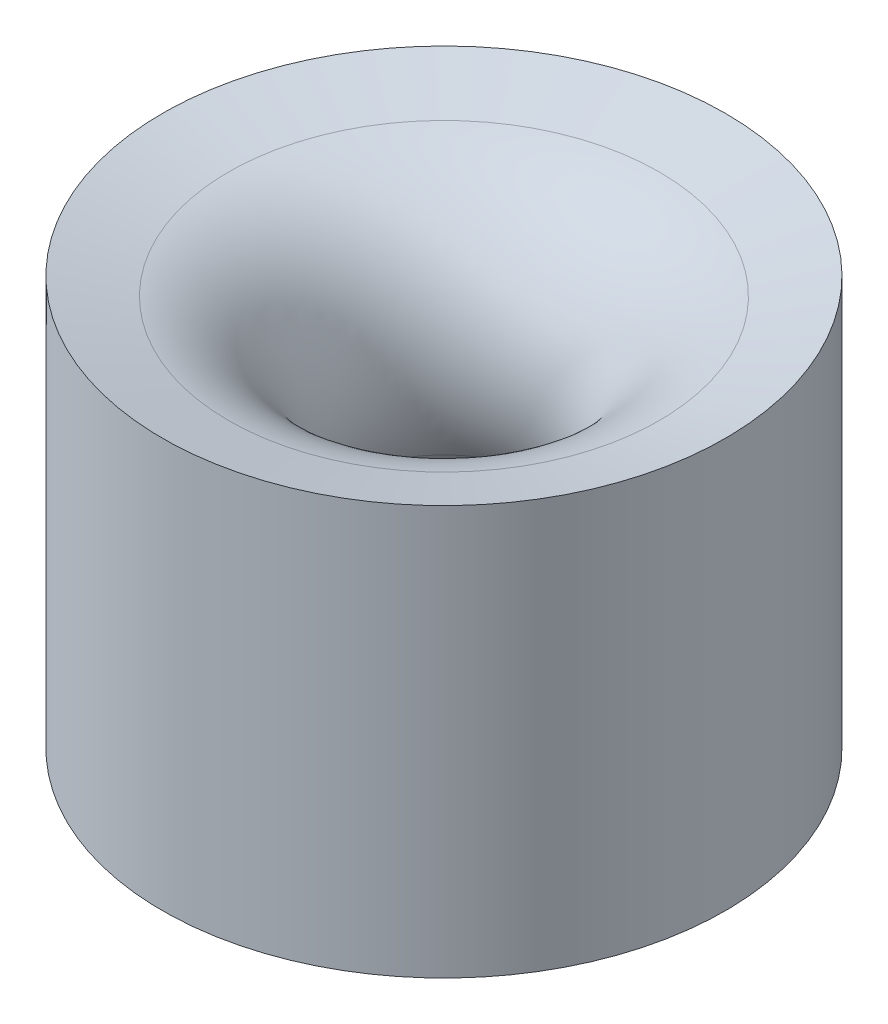
SolidWorks part; units mm, degrees
ref_plane "Front Plane" through (0, 0, 0) normal (0, 0, 1) x (1, 0, 0)
ref_plane "Top Plane" through (0, 0, 0) normal (0, 1, 0) x (1, 0, 0)
ref_plane "Right Plane" through (0, 0, 0) normal (1, 0, 0) x (0, 0, -1)
sketch "Sketch1" plane through (0, 0, 0) normal (0, 0, 1) x (1, 0, 0)
  line L0 (0, -55) -> (0, 55) construction
  line L1 (41.275, 60) -> (41.275, 0)
  line L2 (41.275, 60) -> (31.5772, 57.4015)
  line L3 (41.275, 0) -> (28.5594, 0)
  line L4 (28.5594, 0) -> (16.6849, 25.465)
  line L5 (0, 11.2039) -> (0, 47.7588) construction
  arc A0 (16.6849, 25.465) -> (31.5772, 57.4015) centre (37.53, 35.1852) cw
  dimension "D6" = 37.53
  dimension "D3" = 23
  dimension "D1" = 41.275
  dimension "D2" = 60
  dimension "D4" = 115
  dimension "D5" = 75
revolve "Revolve1" add sketch "Sketch1" angle 360 about L5
